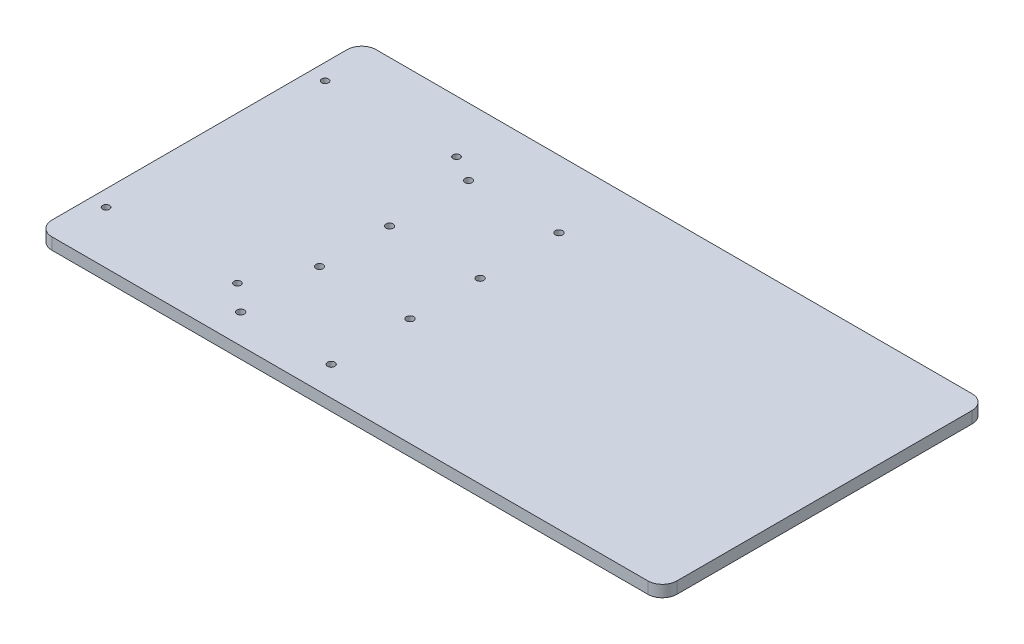
SolidWorks part; units mm, degrees
ref_plane "Front Plane" through (0, 0, 0) normal (0, 0, 1) x (1, 0, 0)
ref_plane "Top Plane" through (0, 0, 0) normal (0, 1, 0) x (1, 0, 0)
ref_plane "Right Plane" through (0, 0, 0) normal (1, 0, 0) x (0, 0, -1)
sketch "Sketch1" plane through (0, 0, 0) normal (0, 1, 0) x (1, 0, 0)
  line L1 (0, 0) -> (214, 0)
  line L2 (0, 0) -> (0, 111)
  line L3 (0, 111) -> (214, 111)
  line L4 (214, 0) -> (214, 111)
  dimension "D1" = 111
  dimension "D2" = 214
extrude "Boss-Extrude1" add sketch "Sketch1" along normal blind 4
sketch "Sketch2" plane through (0, 4, 0) normal (0, 1, 0) x (1, 0, 0)
  circle A0 centre (5.5, 18) radius 1.1727 construction
  circle A1 centre (5.5, 93) radius 1.1727 construction
  circle A2 centre (50.5, 18) radius 1.1727 construction
  circle A3 centre (50.5, 93) radius 1.1727 construction
  circle A4 centre (5.5, 18) radius 1.1727
  circle A5 centre (5.5, 93) radius 1.1727
  circle A6 centre (50.5, 18) radius 1.1727
  circle A7 centre (50.5, 93) radius 1.1727
extrude "Cut-Extrude1" cut sketch "Sketch2" against normal blind 10
sketch "Sketch3" plane through (0, 0, 0) normal (0, -1, 0) x (1, 0, 0)
  circle A0 centre (5.5, -93) radius 1.1727 construction
  circle A1 centre (5.5, -18) radius 1.1727 construction
  circle A2 centre (50.5, -18) radius 1.1727 construction
  circle A3 centre (50.5, -93) radius 1.1727 construction
  circle A4 centre (5.5, -93) radius 1.1727
  circle A5 centre (5.5, -18) radius 1.1727
  circle A6 centre (50.5, -18) radius 1.1727
  circle A7 centre (50.5, -93) radius 1.1727
  circle A8 centre (50.5, -93) radius 3.5
  circle A9 centre (5.5, -93) radius 3.5
  circle A10 centre (5.5, -18) radius 3.5
  circle A11 centre (50.5, -18) radius 3.5
  dimension "D1" = 7
  dimension "D2" = 7
  dimension "D3" = 7
  dimension "D4" = 7
extrude "Cut-Extrude2" cut sketch "Sketch3" against normal blind 2.4
sketch "Sketch4" plane through (0, 0, 0) normal (0, -1, 0) x (1, 0, 0)
  line L0 (214, -111) -> (0, -111) construction
  line L1 (0, -111) -> (0, 0) construction
  line L2 (0, 0) -> (214, 0) construction
  line L3 (214, 0) -> (214, -111) construction
  circle A0 centre (5, -5) radius 1.6
  circle A1 centre (5, -106) radius 1.6
  circle A2 centre (209, -106) radius 1.6
  circle A3 centre (209, -5) radius 1.6
  dimension "D1" = 3.2
  dimension "D2" = 3.2
  dimension "D3" = 3.2
  dimension "D4" = 3.2
  dimension "D5" = 5
  dimension "D7" = 5
  dimension "D8" = 5
  dimension "D9" = 5
  dimension "D10" = 5
  dimension "D11" = 5
  dimension "D12" = 5
  dimension "D6" = 5
extrude "Cut-Extrude3" cut sketch "Sketch4" against normal blind 1.2
fillet "Fillet1" radius 5 4 edges at (214, 2, -111) (214, 2, 0) (0, 2, 0) (0, 2, -111)
sketch "Sketch5" plane through (0, 4, 0) normal (0, 1, 0) x (1, 0, 0)
  arc A0 (59.5838, 62.25) -> (59.5838, 59.75) centre (59.5838, 61) ccw construction
  arc A1 (59.5838, 59.75) -> (59.5838, 62.25) centre (59.5838, 61) ccw construction
  arc A2 (59.5838, 89.25) -> (59.5838, 86.75) centre (59.5838, 88) ccw construction
  arc A3 (59.5838, 86.75) -> (59.5838, 89.25) centre (59.5838, 88) ccw construction
  arc A4 (90.5838, 59.75) -> (90.5838, 62.25) centre (90.5838, 61) ccw construction
  arc A5 (90.5838, 62.25) -> (90.5838, 59.75) centre (90.5838, 61) ccw construction
  arc A6 (90.5838, 89.25) -> (90.5838, 86.75) centre (90.5838, 88) ccw construction
  arc A7 (90.5838, 86.75) -> (90.5838, 89.25) centre (90.5838, 88) ccw construction
  arc A8 (90.5838, 35.75) -> (90.5838, 38.25) centre (90.5838, 37) ccw construction
  arc A9 (90.5838, 38.25) -> (90.5838, 35.75) centre (90.5838, 37) ccw construction
  arc A10 (59.5838, 35.75) -> (59.5838, 38.25) centre (59.5838, 37) ccw construction
  arc A11 (59.5838, 38.25) -> (59.5838, 35.75) centre (59.5838, 37) ccw construction
  arc A12 (59.5838, 8.75) -> (59.5838, 11.25) centre (59.5838, 10) ccw construction
  arc A13 (59.5838, 11.25) -> (59.5838, 8.75) centre (59.5838, 10) ccw construction
  arc A14 (90.5838, 8.75) -> (90.5838, 11.25) centre (90.5838, 10) ccw construction
  arc A15 (90.5838, 11.25) -> (90.5838, 8.75) centre (90.5838, 10) ccw construction
  arc A16 (59.5838, 62.25) -> (59.5838, 59.75) centre (59.5838, 61) ccw
  arc A17 (59.5838, 59.75) -> (59.5838, 62.25) centre (59.5838, 61) ccw
  arc A18 (59.5838, 89.25) -> (59.5838, 86.75) centre (59.5838, 88) ccw
  arc A19 (59.5838, 86.75) -> (59.5838, 89.25) centre (59.5838, 88) ccw
  arc A20 (90.5838, 59.75) -> (90.5838, 62.25) centre (90.5838, 61) ccw
  arc A21 (90.5838, 62.25) -> (90.5838, 59.75) centre (90.5838, 61) ccw
  arc A22 (90.5838, 89.25) -> (90.5838, 86.75) centre (90.5838, 88) ccw
  arc A23 (90.5838, 86.75) -> (90.5838, 89.25) centre (90.5838, 88) ccw
  arc A24 (90.5838, 35.75) -> (90.5838, 38.25) centre (90.5838, 37) ccw
  arc A25 (90.5838, 38.25) -> (90.5838, 35.75) centre (90.5838, 37) ccw
  arc A26 (59.5838, 35.75) -> (59.5838, 38.25) centre (59.5838, 37) ccw
  arc A27 (59.5838, 38.25) -> (59.5838, 35.75) centre (59.5838, 37) ccw
  arc A28 (59.5838, 8.75) -> (59.5838, 11.25) centre (59.5838, 10) ccw
  arc A29 (59.5838, 11.25) -> (59.5838, 8.75) centre (59.5838, 10) ccw
  arc A30 (90.5838, 8.75) -> (90.5838, 11.25) centre (90.5838, 10) ccw
  arc A31 (90.5838, 11.25) -> (90.5838, 8.75) centre (90.5838, 10) ccw
extrude "Cut-Extrude4" cut sketch "Sketch5" against normal blind 8.2
